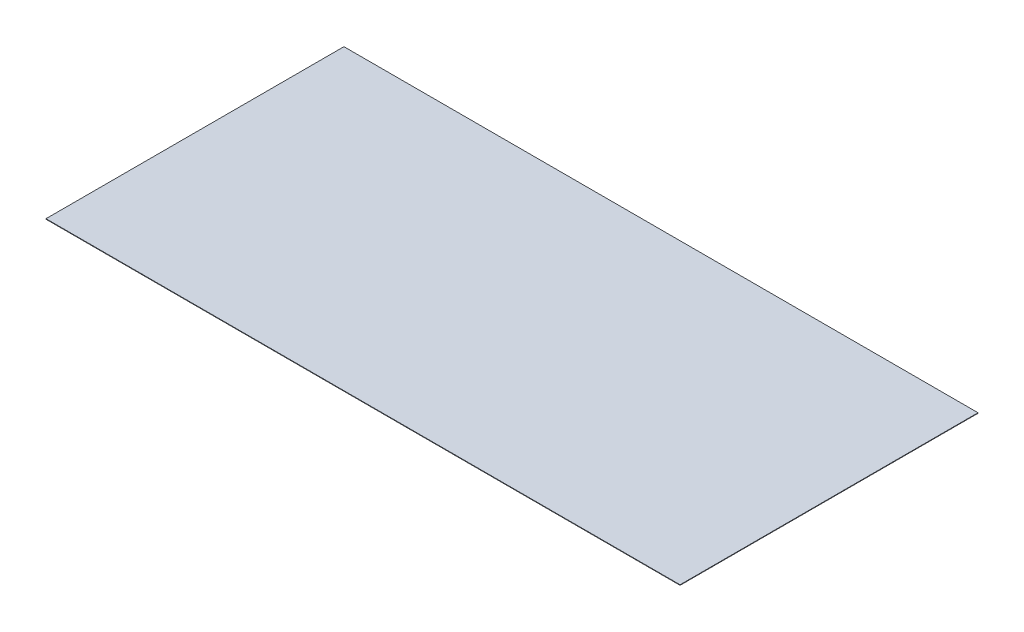
SolidWorks part; units mm, degrees
ref_plane "Front Plane" through (0, 0, 0) normal (0, 0, 1) x (1, 0, 0)
ref_plane "Top Plane" through (0, 0, 0) normal (0, 1, 0) x (1, 0, 0)
ref_plane "Right Plane" through (0, 0, 0) normal (1, 0, 0) x (0, 0, -1)
sketch "Sketch1" plane through (0, 0, 0) normal (0, 1, 0) x (1, 0, 0)
  line L1 (546.8095, -145.3855) -> (-715.1905, -145.3855)
  line L2 (546.8095, -145.3855) -> (546.8095, 447.6145)
  line L3 (546.8095, 447.6145) -> (-715.1905, 447.6145)
  line L4 (-715.1905, -145.3855) -> (-715.1905, 447.6145)
  dimension "D1" = 1262
  dimension "D2" = 593
extrude "Boss-Extrude1" add sketch "Sketch1" along normal blind 1
